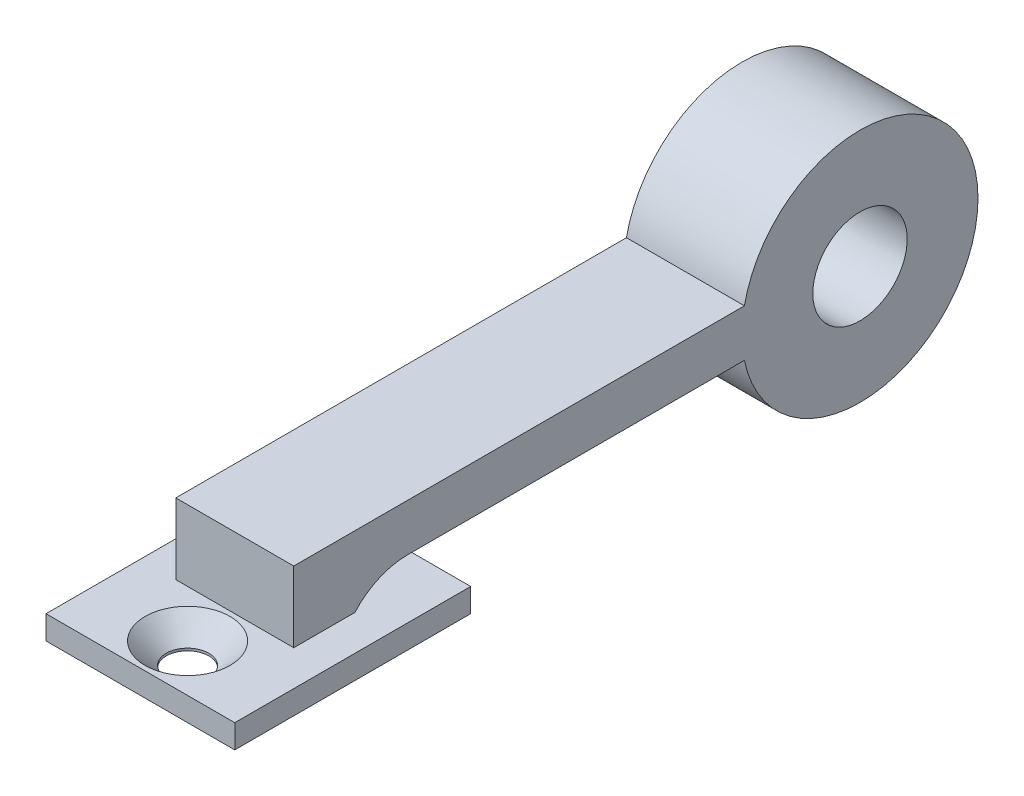
SolidWorks part; units mm, degrees
ref_plane "Front Plane" through (0, 0, 0) normal (0, 0, 1) x (1, 0, 0)
ref_plane "Top Plane" through (0, 0, 0) normal (0, 1, 0) x (1, 0, 0)
ref_plane "Right Plane" through (0, 0, 0) normal (1, 0, 0) x (0, 0, -1)
sketch "Sketch1" plane through (0, 0, 0) normal (1, 0, 0) x (0, 0, -1)
  line L0 (0, 0) -> (0, 3) construction
  line L1 (0, 3) -> (23, 3) construction
  line L2 (18.101, 4) -> (-1, 4)
  line L3 (-1, 4) -> (-1, 0)
  line L4 (-1, 0) -> (1, 0)
  line L5 (1, 0) -> (1, 2)
  line L6 (1, 2) -> (18.101, 2)
  circle A0 centre (23, 3) radius 2
  circle A1 centre (23, 3) radius 5
  point P13 (0, 0)
  dimension "D3" = 4
  dimension "D4" = 10
  dimension "D1" = 23
  dimension "D2" = 3
  dimension "D5" = 2
  dimension "D6" = 2
extrude "Boss-Extrude1" add sketch "Sketch1" along normal blind 5 contours A1 L2 L3 L4 L5 L6 | A0 | A1 region at (0, 2.8098, -7.707) region at (0, 3, -23)
fillet "Fillet1" radius 3 1 edges at (2.5, 2, -1)
sketch "Sketch2" plane through (0, 0, 0) normal (0, -1, 0) x (1, 0, 0)
  line L0 (0, 0) -> (5, 0) construction
  line L1 (5, 1) -> (5, -1) construction
  line L3 (6.5, -5) -> (-1.5, -5)
  line L4 (6.5, -5) -> (6.5, 5)
  line L5 (6.5, 5) -> (-1.5, 5)
  line L6 (-1.5, -5) -> (-1.5, 5)
  line L7 (6.5, -5) -> (-1.5, 5) construction
  line L8 (6.5, 5) -> (-1.5, -5) construction
  point P5 (2.5, 0)
  dimension "D1" = 10
  dimension "D2" = 8
extrude "Boss-Extrude3" add sketch "Sketch2" against normal blind 1
sketch "Sketch3" plane through (0, 1, 0) normal (0, 1, 0) x (1, 0, 0)
  line L0 (6.5, -3) -> (-1.5, -3) construction
  line L1 (6.5, 5) -> (6.5, -5) construction
  line L2 (-1.5, -5) -> (-1.5, 5) construction
  line L3 (6.5, -5) -> (-1.5, -5) construction
  point P11 (2.5, -3)
  dimension "D1" = 2
hole_wizard "CSK for M1.6 Countersunk Flat Head Screw1" positions "Sketch3" profile "Sketch4" countersink size "M1.6" standard "ISO"
sketch "Sketch4" plane through (2.5, 1, 3) normal (1, 0, 0) x (0, 0, 1)
  line L0 (0, 0) -> (0, 30.5408)
  line L1 (0, 30.5408) -> (0.9, 30)
  line L2 (0.9, 30) -> (0.9, 0.9)
  line L3 (0.9, 0.9) -> (1.8, 0)
  line L5 (1.8, 0) -> (0, 0)
  line L6 (-0.9, 0.9) -> (-1.8, 0) construction
  line L10 (0, 30.5408) -> (-0.9, 30) construction
  line L11 (0, -6.35) -> (0, 107.95) construction
  dimension "Hole Dia." = 1.8
  dimension "Hole Depth" = 30
  dimension "Near C'Sink Dia." = 3.6
  dimension "Near C'Sink Angle" = 90
  dimension "Drill Angle" = 118
